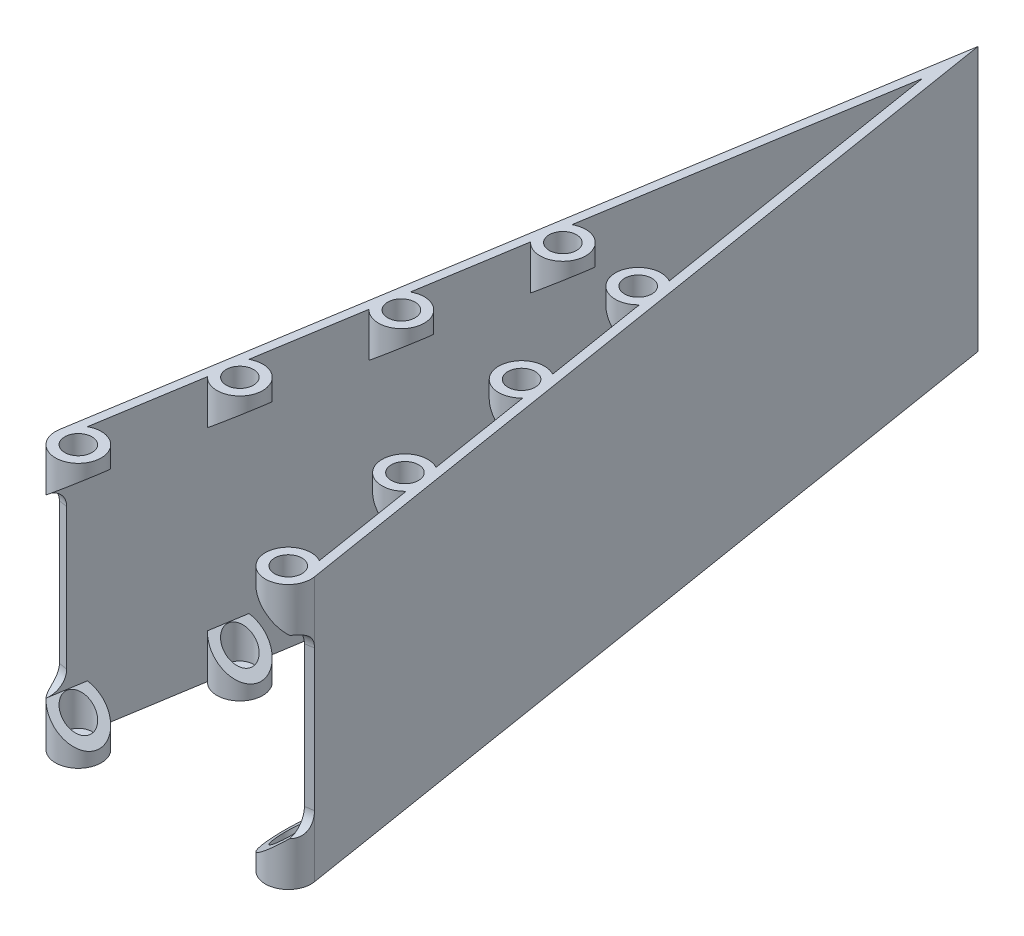
SolidWorks part; units mm, degrees
ref_plane "Front Plane" through (0, 0, 0) normal (0, 0, 1) x (1, 0, 0)
ref_plane "Top Plane" through (0, 0, 0) normal (0, 1, 0) x (1, 0, 0)
ref_plane "Right Plane" through (0, 0, 0) normal (1, 0, 0) x (0, 0, -1)
sketch "Sketch1" plane through (0, 0, 0) normal (0, 1, 0) x (1, 0, 0)
  line L0 (-13.5, 0) -> (13.5, 0) construction
  line L1 (-13.5, 0) -> (0, 83.7185)
  line L2 (0, 83.7185) -> (13.5, 0)
  line L3 (13.5, 0) -> (14.4872, 0.1592)
  line L4 (14.4872, 0.1592) -> (0, 90)
  line L5 (0, 90) -> (-14.4872, 0.1592)
  line L6 (-14.4872, 0.1592) -> (-13.5, 0)
  point P2 (0, 0)
  dimension "D1" = 90
  dimension "D2" = 90
  dimension "D4" = 1
  dimension "D5" = 27
  dimension "D3" = 90
extrude "Boss-Extrude1" add sketch "Sketch1" along normal blind 30
sketch "Sketch2" plane through (0, 0, 0) normal (0, 1, 0) x (1, 0, 0)
  line L0 (0, -1000) -> (0, 49000) construction
  line L1 (0, 83.7185) -> (13.5, 0) construction
  line L2 (0, 83.7185) -> (13.5, 0) construction
  line L3 (11.9204, -0.2547) -> (13.5, 0) construction
  line L4 (13.5, 0) -> (14.4872, 0.1592) construction
  line L5 (14.4872, 0.1592) -> (0, 90) construction
  line L6 (14.4872, 0.1592) -> (0, 90) construction
  circle A0 centre (11.9204, -0.2547) radius 2.6
  circle A1 centre (11.9204, -0.2547) radius 1.55
  circle A22 centre (9.3732, 15.5412) radius 1.55
  circle A23 centre (9.3732, 15.5412) radius 2.6
  circle A24 centre (6.8261, 31.3372) radius 1.55
  circle A25 centre (6.8261, 31.3372) radius 2.6
  circle A26 centre (4.2789, 47.1331) radius 1.55
  circle A27 centre (4.2789, 47.1331) radius 2.6
  circle A28 centre (-4.2789, 47.1331) radius 2.6
  circle A29 centre (-4.2789, 47.1331) radius 1.55
  circle A30 centre (-6.8261, 31.3372) radius 2.6
  circle A31 centre (-6.8261, 31.3372) radius 1.55
  circle A32 centre (-9.3732, 15.5412) radius 2.6
  circle A33 centre (-9.3732, 15.5412) radius 1.55
  circle A34 centre (-11.9204, -0.2547) radius 2.6
  circle A35 centre (-11.9204, -0.2547) radius 1.55
  dimension "D1" = 5.2
  dimension "D2" = 3.1
  dimension "D4" = 16
  dimension "D3" = 4
extrude "Boss-Extrude3" add sketch "Sketch2" along normal blind 5
sketch "Sketch4" plane through (0.3421, 0, 2.1218) normal (0.1592, 0, 0.9872) x (0.9872, 0, -0.1592)
  line L0 (9.1278, 5) -> (9.1278, 0) construction
  line L1 (14.3278, 5) -> (9.1278, 5) construction
  line L2 (13.3278, 30) -> (13.3278, 0) construction
  line L3 (9.1278, 5) -> (9.1278, 0) construction
  line L4 (14.3278, 5) -> (9.1278, 5) construction
  line L5 (13.3278, 30) -> (13.3278, 0) construction
  line L6 (13.3278, 5) -> (9.1278, 1.4758)
  line L7 (13.3278, 5) -> (9.1278, 5)
  line L8 (9.1278, 5) -> (9.1278, 1.4758)
  dimension "D1" = 40
extrude "Cut-Extrude1" cut sketch "Sketch4" against normal up to surface and the other way through all contours L7 L8 L6 up to face at (-8.5675, 5.5556, -30.5881)
sketch "Sketch5" plane through (-0.3421, 0, 2.1218) normal (-0.1592, 0, 0.9872) x (0.9872, 0, 0.1592)
  line L2 (-13.3278, 30) -> (-13.3278, 0) construction
  line L3 (-9.1278, 0) -> (-9.1278, 5) construction
  line L4 (-9.1278, 5) -> (-14.3278, 5) construction
  line L5 (-13.3278, 30) -> (-13.3278, 0) construction
  line L6 (-13.3278, 5) -> (-9.1278, 1.4758)
  line L7 (-13.3278, 5) -> (-9.1278, 5)
  line L8 (-9.1278, 5) -> (-9.1278, 1.4758)
  line L9 (-9.1278, 0) -> (-9.1278, 5)
  line L10 (-9.1278, 5) -> (-14.3278, 5)
  point P7 (-9.4113, 1.4456)
  dimension "D1" = 40
extrude "Cut-Extrude2" cut sketch "Sketch5" against normal up to surface and the other way through all contours L8 L7 L6 up to face at (8.5675, 5.5556, -30.5881)
ref_plane "Plane1" through (0, 15, 0) normal (0, 1, 0) x (1, 0, 0)
mirror "Mirror2" about plane through (0, 15, 0) normal (0, 1, 0) of "Cut-Extrude2", "Cut-Extrude1", "Boss-Extrude3"
fillet "Fillet1" radius 2 4 edges at (13.9936, 5, -0.0796) (13.9936, 25, -0.0796) (-13.9936, 5, -0.0796) (-13.9936, 25, -0.0796)
sketch "Sketch6" plane through (0, 0, 0) normal (0, -1, 0) x (1, 0, 0)
  arc A1 (14.4872, -0.1592) -> (13.1737, -2.0233) centre (11.9204, 0.2547) ccw construction
  arc A2 (11.2791, -13.7727) -> (10.6266, -17.8192) centre (9.3732, -15.5412) ccw construction
  arc A5 (8.7319, -29.5686) -> (8.0794, -33.6151) centre (6.8261, -31.3372) ccw construction
  arc A6 (6.1847, -45.3646) -> (5.5322, -49.4111) centre (4.2789, -47.1331) ccw construction
  arc A10 (-5.5322, -49.4111) -> (-6.1847, -45.3646) centre (-4.2789, -47.1331) ccw construction
  arc A11 (14.4872, -0.1592) -> (13.1737, -2.0233) centre (11.9204, 0.2547) ccw
  arc A12 (11.2791, -13.7727) -> (10.6266, -17.8192) centre (9.3732, -15.5412) ccw
  arc A13 (-8.0794, -33.6151) -> (-8.7319, -29.5686) centre (-6.8261, -31.3372) ccw construction
  arc A14 (-10.6266, -17.8192) -> (-11.2791, -13.7727) centre (-9.3732, -15.5412) ccw construction
  arc A15 (8.7319, -29.5686) -> (8.0794, -33.6151) centre (6.8261, -31.3372) ccw
  arc A16 (6.1847, -45.3646) -> (5.5322, -49.4111) centre (4.2789, -47.1331) ccw
  arc A17 (-13.1737, -2.0233) -> (-14.4872, -0.1592) centre (-11.9204, 0.2547) ccw construction
  arc A18 (-5.5322, -49.4111) -> (-6.1847, -45.3646) centre (-4.2789, -47.1331) ccw
  arc A19 (-8.0794, -33.6151) -> (-8.7319, -29.5686) centre (-6.8261, -31.3372) ccw
  circle A22 centre (4.2789, -47.1331) radius 2.6
  circle A24 centre (6.8261, -31.3372) radius 2.6
  circle A27 centre (9.3732, -15.5412) radius 2.6
  circle A28 centre (11.9204, 0.2547) radius 2.6
  arc A30 (-10.6266, -17.8192) -> (-11.2791, -13.7727) centre (-9.3732, -15.5412) ccw
  arc A31 (-13.1737, -2.0233) -> (-14.4872, -0.1592) centre (-11.9204, 0.2547) ccw
  circle A32 centre (-11.9204, 0.2547) radius 2.6
  circle A33 centre (-9.3732, -15.5412) radius 2.6
  circle A34 centre (-6.8261, -31.3372) radius 2.6
  circle A35 centre (-4.2789, -47.1331) radius 2.6
extrude "Boss-Extrude4" add sketch "Sketch6" against normal blind 1
equation "\"D2@Sketch1\"=\"D1@Sketch1\""
